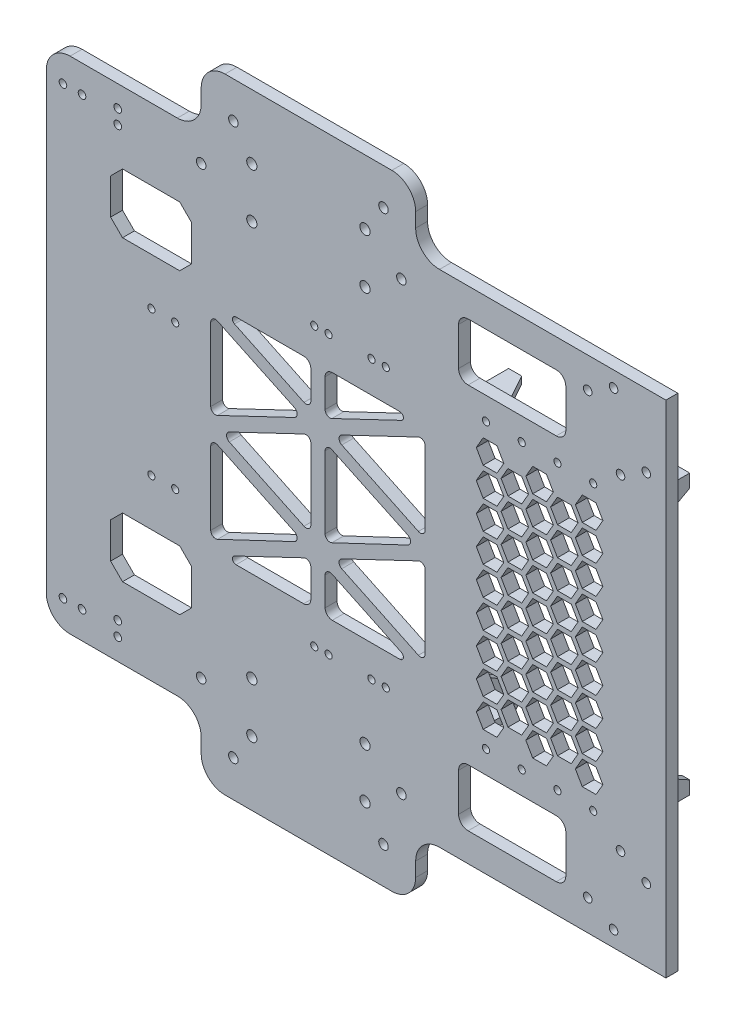
SolidWorks part; units mm, degrees
ref_plane "前视基准面" through (0, 0, 0) normal (0, 0, 1) x (1, 0, 0)
ref_plane "上视基准面" through (0, 0, 0) normal (0, 1, 0) x (1, 0, 0)
ref_plane "右视基准面" through (0, 0, 0) normal (1, 0, 0) x (0, 0, -1)
sketch "草图1" plane through (0, 0, 0) normal (0, 0, 1) x (1, 0, 0)
  line L2 (-130, 95) -> (-130, -95)
  line L3 (-120, -105) -> (-75, -105)
  line L4 (130, 95) -> (130, -95)
  line L5 (126.7518, 102.3765) -> (130, 105) construction
  line L6 (-130, -105) -> (-126.7518, -102.3765) construction
  line L9 (-65, -115) -> (-65, -121)
  line L10 (-55, -131) -> (15, -131)
  line L11 (25, -121) -> (25, -115)
  line L13 (35, -105) -> (120, -105)
  line L14 (126.7518, -102.3765) -> (130, -105) construction
  line L15 (-130, 105) -> (-126.7518, 102.3765) construction
  line L16 (-130, 0) -> (130, 0) construction
  line L17 (35, 105) -> (120, 105)
  line L18 (25, 121) -> (25, 115)
  line L19 (-55, 131) -> (15, 131)
  line L20 (-65, 115) -> (-65, 121)
  line L21 (-120, 105) -> (-75, 105)
  arc A1 (-120, -105) -> (-130, -95) centre (-120, -95) cw
  arc A3 (120, -105) -> (130, -95) centre (120, -95) ccw
  arc A8 (-65, -115) -> (-75, -105) centre (-75, -115) ccw
  arc A9 (25, -115) -> (35, -105) centre (35, -115) cw
  arc A10 (-55, -131) -> (-65, -121) centre (-55, -121) cw
  arc A11 (15, -131) -> (25, -121) centre (15, -121) ccw
  arc A12 (15, 131) -> (25, 121) centre (15, 121) cw
  arc A13 (-55, 131) -> (-65, 121) centre (-55, 121) ccw
  arc A14 (25, 115) -> (35, 105) centre (35, 115) ccw
  arc A15 (-65, 115) -> (-75, 105) centre (-75, 115) cw
  arc A16 (120, 105) -> (130, 95) centre (120, 95) cw
  arc A17 (-120, 105) -> (-130, 95) centre (-120, 95) ccw
  point P0 (0, 0)
  point P40 (25, -105)
  point P45 (25, 105)
  dimension "D2" = 10
  dimension "D3" = 65
  dimension "D4" = 10
  dimension "D5" = 105
  dimension "D7" = 10
  dimension "D8" = 10
  dimension "D10" = 10
  dimension "D12" = 10
  dimension "D13" = 105
  dimension "D18" = 90
  dimension "D19" = 6
extrude "凸台-拉伸1" add sketch "草图1" along normal blind 5
sketch "草图4" plane through (0, 0, 0) normal (0, 0, -1) x (-1, 0, 0)
  line L0 (-39, -47.5) -> (-39, -58.5)
  line L1 (-39, -58.5) -> (-50, -58.5)
  line L2 (-50, -58.5) -> (-50, -55.5)
  line L3 (-50, -55.5) -> (-42, -55.5)
  line L4 (-42, -55.5) -> (-42, -47.5)
  line L5 (-42, -47.5) -> (-39, -47.5)
  line L6 (-130, 0) -> (-25.5592, 0) construction
  line L7 (-130, -95) -> (-130, 95) construction
  line L10 (-130, -95) -> (-130, 95) construction
  dimension "D1" = 11
  dimension "D2" = 11
  dimension "D3" = 3
  dimension "D4" = 3
  dimension "D5" = 80
  dimension "D7" = 55.5
extrude "凸台-拉伸2" add sketch "草图4" along normal blind 20
sketch "草图5" plane through (0, -58.5, 0) normal (0, -1, 0) x (1, 0, 0)
  line L0 (50, -10) -> (44.5, -20)
  line L1 (50, -20) -> (50, 0) construction
  line L2 (50, -20) -> (39, -20) construction
  line L3 (44.5, -20) -> (50, -20)
  line L4 (50, -20) -> (50, -10)
  dimension "D1" = 10
  dimension "D2" = 5.5
extrude "切除-拉伸3" cut sketch "草图5" against normal blind 10
sketch "草图6" plane through (39, 0, 0) normal (-1, 0, 0) x (0, 0, 1)
  line L0 (-20, -53) -> (-10, -47.5)
  line L1 (-20, -58.5) -> (-20, -47.5) construction
  line L2 (-20, -47.5) -> (0, -47.5) construction
  line L3 (-10, -47.5) -> (-20, -47.5)
  line L4 (-20, -47.5) -> (-20, -53)
  dimension "D1" = 10
  dimension "D2" = 5.5
extrude "切除-拉伸4" cut sketch "草图6" against normal blind 10
ref_plane "基准面2" through (77, 0, 0) normal (1, 0, 0) x (0, 0, -1)
mirror "镜向1" about plane through (77, 0, 0) normal (1, 0, 0) of "凸台-拉伸2", "切除-拉伸4", "切除-拉伸3"
mirror "镜向2" about plane through (0, 0, 0) normal (0, 1, 0) of "镜向1"
sketch "草图7" plane through (0, 0, 0) normal (0, 0, -1) x (-1, 0, 0)
  line L4 (-112, -55.5) -> (-104, -55.5) construction
  line L5 (-112, 47.5) -> (-112, 55.5) construction
  line L6 (-112, 55.5) -> (-104, 55.5) construction
  line L7 (-92.013, 36) -> (-94.8997, 41)
  line L8 (-94.8997, 41) -> (-100.6732, 41)
  line L9 (-100.6732, 41) -> (-103.56, 36)
  line L10 (-103.56, 36) -> (-100.6732, 31)
  line L11 (-100.6732, 31) -> (-94.8997, 31)
  line L12 (-94.8997, 31) -> (-92.013, 36)
  line L13 (-77.0019, 36) -> (-97.7865, 36) construction
  line L14 (-74.1151, 31) -> (-71.2284, 36)
  line L15 (-71.2284, 36) -> (-74.1151, 41)
  line L16 (-74.1151, 41) -> (-79.8886, 41)
  line L17 (-79.8886, 41) -> (-82.7754, 36)
  line L18 (-82.7754, 36) -> (-79.8886, 31)
  line L19 (-79.8886, 31) -> (-74.1151, 31)
  line L20 (-92.013, 24) -> (-94.8997, 29)
  line L21 (-93.1677, 30) -> (-90.2809, 25)
  line L22 (-90.2809, 25) -> (-84.5074, 25)
  line L23 (-84.5074, 25) -> (-81.6207, 30)
  line L24 (-81.6207, 30) -> (-84.5074, 35)
  line L25 (-84.5074, 35) -> (-90.2809, 35)
  line L26 (-90.2809, 35) -> (-93.1677, 30)
  line L27 (-84.5074, 37) -> (-81.6207, 42)
  line L28 (-81.6207, 42) -> (-84.5074, 47)
  line L29 (-84.5074, 47) -> (-90.2809, 47)
  line L30 (-90.2809, 47) -> (-93.1677, 42)
  line L31 (-93.1677, 42) -> (-90.2809, 37)
  line L32 (-90.2809, 37) -> (-84.5074, 37)
  line L33 (-79.8886, 43) -> (-74.1151, 43)
  line L34 (-74.1151, 43) -> (-71.2284, 48)
  line L35 (-71.2284, 48) -> (-74.1151, 53)
  line L36 (-74.1151, 53) -> (-79.8886, 53)
  line L37 (-79.8886, 53) -> (-82.7754, 48)
  line L38 (-82.7754, 48) -> (-79.8886, 43)
  line L39 (-94.8997, 43) -> (-92.013, 48)
  line L40 (-92.013, 48) -> (-94.8997, 53)
  line L41 (-94.8997, 53) -> (-100.6732, 53)
  line L42 (-100.6732, 53) -> (-103.56, 48)
  line L43 (-103.56, 48) -> (-100.6732, 43)
  line L44 (-100.6732, 43) -> (-94.8997, 43)
  line L45 (-72.3831, 42) -> (-69.4963, 37)
  line L46 (-69.4963, 37) -> (-63.7228, 37)
  line L47 (-63.7228, 37) -> (-60.8361, 42)
  line L48 (-60.8361, 42) -> (-63.7228, 47)
  line L49 (-63.7228, 47) -> (-69.4963, 47)
  line L50 (-69.4963, 47) -> (-72.3831, 42)
  line L51 (-94.8997, 29) -> (-100.6732, 29)
  line L52 (-100.6732, 29) -> (-103.56, 24)
  line L53 (-103.56, 24) -> (-100.6732, 19)
  line L54 (-100.6732, 19) -> (-94.8997, 19)
  line L55 (-94.8997, 19) -> (-92.013, 24)
  line L56 (-93.1677, 18) -> (-90.2809, 13)
  line L57 (-90.2809, 13) -> (-84.5074, 13)
  line L58 (-84.5074, 13) -> (-81.6207, 18)
  line L59 (-81.6207, 18) -> (-84.5074, 23)
  line L60 (-84.5074, 23) -> (-90.2809, 23)
  line L61 (-90.2809, 23) -> (-93.1677, 18)
  line L62 (-74.1151, 19) -> (-71.2284, 24)
  line L63 (-71.2284, 24) -> (-74.1151, 29)
  line L64 (-74.1151, 29) -> (-79.8886, 29)
  line L65 (-79.8886, 29) -> (-82.7754, 24)
  line L66 (-82.7754, 24) -> (-79.8886, 19)
  line L67 (-79.8886, 19) -> (-74.1151, 19)
  line L68 (-72.3831, 30) -> (-69.4963, 25)
  line L69 (-69.4963, 25) -> (-63.7228, 25)
  line L70 (-63.7228, 25) -> (-60.8361, 30)
  line L71 (-60.8361, 30) -> (-63.7228, 35)
  line L72 (-63.7228, 35) -> (-69.4963, 35)
  line L73 (-69.4963, 35) -> (-72.3831, 30)
  line L74 (-92.013, 12) -> (-94.8997, 17)
  line L75 (-94.8997, 17) -> (-100.6732, 17)
  line L76 (-100.6732, 17) -> (-103.56, 12)
  line L77 (-103.56, 12) -> (-100.6732, 7)
  line L78 (-100.6732, 7) -> (-94.8997, 7)
  line L79 (-94.8997, 7) -> (-92.013, 12)
  line L80 (-93.1677, 6) -> (-90.2809, 1)
  line L81 (-90.2809, 1) -> (-84.5074, 1)
  line L82 (-84.5074, 1) -> (-81.6207, 6)
  line L83 (-81.6207, 6) -> (-84.5074, 11)
  line L84 (-84.5074, 11) -> (-90.2809, 11)
  line L85 (-90.2809, 11) -> (-93.1677, 6)
  line L86 (-74.1151, 7) -> (-71.2284, 12)
  line L87 (-71.2284, 12) -> (-74.1151, 17)
  line L88 (-74.1151, 17) -> (-79.8886, 17)
  line L89 (-79.8886, 17) -> (-82.7754, 12)
  line L90 (-82.7754, 12) -> (-79.8886, 7)
  line L91 (-79.8886, 7) -> (-74.1151, 7)
  line L92 (-72.3831, 18) -> (-69.4963, 13)
  line L93 (-69.4963, 13) -> (-63.7228, 13)
  line L94 (-63.7228, 13) -> (-60.8361, 18)
  line L95 (-60.8361, 18) -> (-63.7228, 23)
  line L96 (-63.7228, 23) -> (-69.4963, 23)
  line L97 (-69.4963, 23) -> (-72.3831, 18)
  line L98 (-92.013, 0) -> (-94.8997, 5)
  line L99 (-94.8997, 5) -> (-100.6732, 5)
  line L100 (-100.6732, 5) -> (-103.56, 0)
  line L101 (-103.56, 0) -> (-100.6732, -5)
  line L102 (-100.6732, -5) -> (-94.8997, -5)
  line L103 (-94.8997, -5) -> (-92.013, 0)
  line L104 (-93.1677, -6) -> (-90.2809, -11)
  line L105 (-90.2809, -11) -> (-84.5074, -11)
  line L106 (-84.5074, -11) -> (-81.6207, -6)
  line L107 (-81.6207, -6) -> (-84.5074, -1)
  line L108 (-84.5074, -1) -> (-90.2809, -1)
  line L109 (-90.2809, -1) -> (-93.1677, -6)
  line L110 (-74.1151, -5) -> (-71.2284, 0)
  line L111 (-71.2284, 0) -> (-74.1151, 5)
  line L112 (-74.1151, 5) -> (-79.8886, 5)
  line L113 (-79.8886, 5) -> (-82.7754, 0)
  line L114 (-82.7754, 0) -> (-79.8886, -5)
  line L115 (-79.8886, -5) -> (-74.1151, -5)
  line L116 (-72.3831, 6) -> (-69.4963, 1)
  line L117 (-69.4963, 1) -> (-63.7228, 1)
  line L118 (-63.7228, 1) -> (-60.8361, 6)
  line L119 (-60.8361, 6) -> (-63.7228, 11)
  line L120 (-63.7228, 11) -> (-69.4963, 11)
  line L121 (-69.4963, 11) -> (-72.3831, 6)
  line L122 (-92.013, -12) -> (-94.8997, -7)
  line L123 (-94.8997, -7) -> (-100.6732, -7)
  line L124 (-100.6732, -7) -> (-103.56, -12)
  line L125 (-103.56, -12) -> (-100.6732, -17)
  line L126 (-100.6732, -17) -> (-94.8997, -17)
  line L127 (-94.8997, -17) -> (-92.013, -12)
  line L128 (-93.1677, -18) -> (-90.2809, -23)
  line L129 (-90.2809, -23) -> (-84.5074, -23)
  line L130 (-84.5074, -23) -> (-81.6207, -18)
  line L131 (-81.6207, -18) -> (-84.5074, -13)
  line L132 (-84.5074, -13) -> (-90.2809, -13)
  line L133 (-90.2809, -13) -> (-93.1677, -18)
  line L134 (-74.1151, -17) -> (-71.2284, -12)
  line L135 (-71.2284, -12) -> (-74.1151, -7)
  line L136 (-74.1151, -7) -> (-79.8886, -7)
  line L137 (-79.8886, -7) -> (-82.7754, -12)
  line L138 (-82.7754, -12) -> (-79.8886, -17)
  line L139 (-79.8886, -17) -> (-74.1151, -17)
  line L140 (-72.3831, -6) -> (-69.4963, -11)
  line L141 (-69.4963, -11) -> (-63.7228, -11)
  line L142 (-63.7228, -11) -> (-60.8361, -6)
  line L143 (-60.8361, -6) -> (-63.7228, -1)
  line L144 (-63.7228, -1) -> (-69.4963, -1)
  line L145 (-69.4963, -1) -> (-72.3831, -6)
  line L146 (-92.013, -24) -> (-94.8997, -19)
  line L147 (-94.8997, -19) -> (-100.6732, -19)
  line L148 (-100.6732, -19) -> (-103.56, -24)
  line L149 (-103.56, -24) -> (-100.6732, -29)
  line L150 (-100.6732, -29) -> (-94.8997, -29)
  line L151 (-94.8997, -29) -> (-92.013, -24)
  line L152 (-93.1677, -30) -> (-90.2809, -35)
  line L153 (-90.2809, -35) -> (-84.5074, -35)
  line L154 (-84.5074, -35) -> (-81.6207, -30)
  line L155 (-81.6207, -30) -> (-84.5074, -25)
  line L156 (-84.5074, -25) -> (-90.2809, -25)
  line L157 (-90.2809, -25) -> (-93.1677, -30)
  line L158 (-74.1151, -29) -> (-71.2284, -24)
  line L159 (-71.2284, -24) -> (-74.1151, -19)
  line L160 (-74.1151, -19) -> (-79.8886, -19)
  line L161 (-79.8886, -19) -> (-82.7754, -24)
  line L162 (-82.7754, -24) -> (-79.8886, -29)
  line L163 (-79.8886, -29) -> (-74.1151, -29)
  line L164 (-72.3831, -18) -> (-69.4963, -23)
  line L165 (-69.4963, -23) -> (-63.7228, -23)
  line L166 (-63.7228, -23) -> (-60.8361, -18)
  line L167 (-60.8361, -18) -> (-63.7228, -13)
  line L168 (-63.7228, -13) -> (-69.4963, -13)
  line L169 (-69.4963, -13) -> (-72.3831, -18)
  line L170 (-92.013, -36) -> (-94.8997, -31)
  line L171 (-94.8997, -31) -> (-100.6732, -31)
  line L172 (-100.6732, -31) -> (-103.56, -36)
  line L173 (-103.56, -36) -> (-100.6732, -41)
  line L174 (-100.6732, -41) -> (-94.8997, -41)
  line L175 (-94.8997, -41) -> (-92.013, -36)
  line L176 (-93.1677, -42) -> (-90.2809, -47)
  line L177 (-90.2809, -47) -> (-84.5074, -47)
  line L178 (-84.5074, -47) -> (-81.6207, -42)
  line L179 (-81.6207, -42) -> (-84.5074, -37)
  line L180 (-84.5074, -37) -> (-90.2809, -37)
  line L181 (-90.2809, -37) -> (-93.1677, -42)
  line L182 (-74.1151, -41) -> (-71.2284, -36)
  line L183 (-71.2284, -36) -> (-74.1151, -31)
  line L184 (-74.1151, -31) -> (-79.8886, -31)
  line L185 (-79.8886, -31) -> (-82.7754, -36)
  line L186 (-82.7754, -36) -> (-79.8886, -41)
  line L187 (-79.8886, -41) -> (-74.1151, -41)
  line L188 (-72.3831, -30) -> (-69.4963, -35)
  line L189 (-69.4963, -35) -> (-63.7228, -35)
  line L190 (-63.7228, -35) -> (-60.8361, -30)
  line L191 (-60.8361, -30) -> (-63.7228, -25)
  line L192 (-63.7228, -25) -> (-69.4963, -25)
  line L193 (-69.4963, -25) -> (-72.3831, -30)
  line L194 (-92.013, -48) -> (-94.8997, -43)
  line L195 (-94.8997, -43) -> (-100.6732, -43)
  line L196 (-100.6732, -43) -> (-103.56, -48)
  line L197 (-103.56, -48) -> (-100.6732, -53)
  line L198 (-100.6732, -53) -> (-94.8997, -53)
  line L199 (-94.8997, -53) -> (-92.013, -48)
  line L206 (-74.1151, -53) -> (-71.2284, -48)
  line L207 (-71.2284, -48) -> (-74.1151, -43)
  line L208 (-74.1151, -43) -> (-79.8886, -43)
  line L209 (-79.8886, -43) -> (-82.7754, -48)
  line L210 (-82.7754, -48) -> (-79.8886, -53)
  line L211 (-79.8886, -53) -> (-74.1151, -53)
  line L212 (-72.3831, -42) -> (-69.4963, -47)
  line L213 (-69.4963, -47) -> (-63.7228, -47)
  line L214 (-63.7228, -47) -> (-60.8361, -42)
  line L215 (-60.8361, -42) -> (-63.7228, -37)
  line L216 (-63.7228, -37) -> (-69.4963, -37)
  line L217 (-69.4963, -37) -> (-72.3831, -42)
  line L218 (-61.9908, 36) -> (-59.104, 31)
  line L219 (-61.9908, 48) -> (-59.104, 43)
  line L220 (-59.104, 43) -> (-53.3305, 43)
  line L221 (-53.3305, 43) -> (-50.4438, 48)
  line L222 (-50.4438, 48) -> (-53.3305, 53)
  line L223 (-53.3305, 53) -> (-59.104, 53)
  line L224 (-59.104, 53) -> (-61.9908, 48)
  line L225 (-59.104, 31) -> (-53.3305, 31)
  line L226 (-53.3305, 31) -> (-50.4438, 36)
  line L227 (-50.4438, 36) -> (-53.3305, 41)
  line L228 (-53.3305, 41) -> (-59.104, 41)
  line L229 (-59.104, 41) -> (-61.9908, 36)
  line L230 (-61.9908, 24) -> (-59.104, 19)
  line L231 (-59.104, 19) -> (-53.3305, 19)
  line L232 (-53.3305, 19) -> (-50.4438, 24)
  line L233 (-50.4438, 24) -> (-53.3305, 29)
  line L234 (-53.3305, 29) -> (-59.104, 29)
  line L235 (-59.104, 29) -> (-61.9908, 24)
  line L236 (-61.9908, 12) -> (-59.104, 7)
  line L237 (-59.104, 7) -> (-53.3305, 7)
  line L238 (-53.3305, 7) -> (-50.4438, 12)
  line L239 (-50.4438, 12) -> (-53.3305, 17)
  line L240 (-53.3305, 17) -> (-59.104, 17)
  line L241 (-59.104, 17) -> (-61.9908, 12)
  line L242 (-61.9908, 0) -> (-59.104, -5)
  line L243 (-59.104, -5) -> (-53.3305, -5)
  line L244 (-53.3305, -5) -> (-50.4438, 0)
  line L245 (-50.4438, 0) -> (-53.3305, 5)
  line L246 (-53.3305, 5) -> (-59.104, 5)
  line L247 (-59.104, 5) -> (-61.9908, 0)
  line L248 (-61.9908, -12) -> (-59.104, -17)
  line L249 (-59.104, -17) -> (-53.3305, -17)
  line L250 (-53.3305, -17) -> (-50.4438, -12)
  line L251 (-50.4438, -12) -> (-53.3305, -7)
  line L252 (-53.3305, -7) -> (-59.104, -7)
  line L253 (-59.104, -7) -> (-61.9908, -12)
  line L254 (-61.9908, -24) -> (-59.104, -29)
  line L255 (-59.104, -29) -> (-53.3305, -29)
  line L256 (-53.3305, -29) -> (-50.4438, -24)
  line L257 (-50.4438, -24) -> (-53.3305, -19)
  line L258 (-53.3305, -19) -> (-59.104, -19)
  line L259 (-59.104, -19) -> (-61.9908, -24)
  line L260 (-61.9908, -36) -> (-59.104, -41)
  line L261 (-59.104, -41) -> (-53.3305, -41)
  line L262 (-53.3305, -41) -> (-50.4438, -36)
  line L263 (-50.4438, -36) -> (-53.3305, -31)
  line L264 (-53.3305, -31) -> (-59.104, -31)
  line L265 (-59.104, -31) -> (-61.9908, -36)
  line L266 (-61.9908, -48) -> (-59.104, -53)
  line L267 (-59.104, -53) -> (-53.3305, -53)
  line L268 (-53.3305, -53) -> (-50.4438, -48)
  line L269 (-50.4438, -48) -> (-53.3305, -43)
  line L270 (-53.3305, -43) -> (-59.104, -43)
  line L271 (-59.104, -43) -> (-61.9908, -48)
  line L272 (-93.1677, -54) -> (-90.2809, -59) [skipped]
  line L273 (-90.2809, -59) -> (-84.5074, -59) [skipped]
  line L274 (-84.5074, -59) -> (-81.6207, -54) [skipped]
  line L275 (-81.6207, -54) -> (-84.5074, -49) [skipped]
  line L276 (-84.5074, -49) -> (-90.2809, -49) [skipped]
  line L277 (-90.2809, -49) -> (-93.1677, -54) [skipped]
  circle A0 centre (-97.7865, 36) radius 5 construction
  circle A1 centre (-77.0019, 36) radius 5 construction
  circle A2 centre (-87.3942, 30) radius 5 construction
  circle A3 centre (-87.3942, 42) radius 5 construction
  circle A4 centre (-77.0019, 48) radius 5 construction
  circle A5 centre (-97.7865, 48) radius 5 construction
  circle A6 centre (-66.6096, 42) radius 5 construction
  circle A7 centre (-56.2173, 48) radius 5 construction
  point P4 (-87.3942, 37)
  dimension "D1" = 2
  dimension "D3" = 10
  dimension "D4" = 10
  dimension "D5" = 2
  dimension "D7" = 10
  dimension "D11" = 10
  dimension "D14" = 10
  dimension "D15" = 10
  dimension "D20" = 10
  dimension "D2" = 2
  dimension "D6" = 2
  dimension "D8" = 2
  dimension "D9" = 2
  dimension "D10" = 2
  dimension "D12" = 2
  dimension "D13" = 2
  dimension "D16" = 2
  dimension "D17" = 2
  dimension "D19" = 2
  dimension "D21" = 9
  dimension "D22" = 2.5
  dimension "D23" = 2.5
  dimension "D24" = 8.44
  dimension "D18" = 8
extrude "切除-拉伸5" cut sketch "草图7" against normal blind 5
sketch "草图8" plane through (0, 0, 0) normal (0, 0, -1) x (-1, 0, 0)
  line L0 (-75.3677, 120) -> (-75.3677, -120)
  line L1 (-100.0285, 77.2863) -> (-100.0285, -77.2863)
  line L2 (-100.0285, 77.2863) -> (-75.3677, 120)
  line L3 (-100.0285, -77.2863) -> (-75.3677, -120)
  line L4 (-37.1297, 0) -> (-146.8562, 0) construction
  dimension "D1" = 30
  dimension "D2" = 30
  dimension "D3" = 120
  dimension "D4" = 120
sketch "草图9" plane through (0, 0, 0) normal (0, 0, -1) x (-1, 0, 0)
  line L0 (148.8518, 0) -> (-37.1297, 0) construction
  line L1 (-29, 41) -> (-29, 4)
  line L2 (-25, -45) -> (13, -45)
  line L3 (61, -41) -> (61, -4)
  line L4 (57, 45) -> (19, 45)
  line L14 (-29, 41) -> (9.8049, 22.5)
  line L15 (57, 0) -> (19, -18.1163)
  line L16 (130, 95) -> (130, -95) construction
  line L17 (63, 93) -> (118, 93)
  line L18 (63, 93) -> (63, 66)
  line L19 (63, 66) -> (118, 66)
  line L20 (118, 93) -> (118, 66)
  line L21 (75, 105) -> (120, 105) construction
  line L22 (63, -66) -> (118, -66)
  line L23 (118, -93) -> (118, -66)
  line L24 (63, -93) -> (118, -93)
  line L25 (63, -93) -> (63, -66)
  line L26 (-120, 105) -> (-35, 105) construction
  line L27 (-43, 93) -> (-88, 93)
  line L28 (-43, 93) -> (-43, 69)
  line L29 (-43, 69) -> (-88, 69)
  line L30 (-88, 93) -> (-88, 69)
  line L31 (-130, -95) -> (-130, 95) construction
  line L32 (-43, -69) -> (-88, -69)
  line L33 (-88, -93) -> (-88, -69)
  line L34 (-43, -93) -> (-88, -93)
  line L35 (-43, -93) -> (-43, -69)
  line L36 (-25, 45) -> (13, 26.8837)
  line L37 (-25, -45) -> (13, -26.8837)
  line L38 (61, 41) -> (22.0746, 22.5575)
  line L39 (-25.5359, 0) -> (13, -18.258)
  line L40 (57, 45) -> (19, 26.8837)
  line L41 (57, -45) -> (19, -26.8837)
  line L42 (16, 61.4977) -> (16, -60.5731) construction
  line L43 (13, 45) -> (13, 26.8837)
  line L44 (19, 45) -> (19, 26.8837)
  line L45 (13, 18.258) -> (13, -18.258)
  line L46 (9.8049, 22.5) -> (-29, 4)
  line L47 (19, 18.1163) -> (57, 0)
  line L48 (22.0746, 22.5575) -> (61, 4)
  line L49 (13, 18.258) -> (-25.5359, 0)
  line L50 (19, 18.1163) -> (19, -18.1163)
  line L51 (22.0746, -22.5575) -> (61, -41)
  line L52 (9.8049, -22.5) -> (-29, -41)
  line L53 (9.8049, -22.5) -> (-29, -4)
  line L54 (22.0746, -22.5575) -> (61, -4)
  line L55 (13, -26.8837) -> (13, -45)
  line L56 (19, -26.8837) -> (19, -45)
  line L57 (13, 45) -> (-25, 45)
  line L58 (-29, -4) -> (-29, -41)
  line L59 (19, -45) -> (57, -45)
  line L60 (61, 4) -> (61, 41)
  line L61 (-44, 41) -> (-44, -37.8122) construction
  dimension "D1" = 45
  dimension "D2" = 45
  dimension "D3" = 15
  dimension "D4" = 90
  dimension "D5" = 1
  dimension "D7" = 12
  dimension "D8" = 12
  dimension "D9" = 27
  dimension "D10" = 55
  dimension "D11" = 12
  dimension "D12" = 45
  dimension "D13" = 42
  dimension "D14" = 24
  dimension "D21" = 4
  dimension "D22" = 4
  dimension "D23" = 4
  dimension "D24" = 4
  dimension "D26" = 4
  dimension "D27" = 3
  dimension "D28" = 45
extrude "切除-拉伸6" cut sketch "草图9" against normal blind 5 contours L27 L30 L29 L28 | L34 L35 L32 L33 | L4 L44 L40 | L48 L60 L38 | L47 L50 L15 | L54 L51 L3 | L56 L59 L41 | L55 L37 L2 | L53 L58 L52 | L45 L49 L39 | L46 L14 L1 | L43 L57 L36 | L57 L36 L43 region at (16.065, 22.5, 0) region at (-0.3333, -38.9612, 0) region at (-48.0249, -22.5192, 0) region at (-31.6667, 38.9612, 0) region at (-31.6667, 0, 0) region at (65.5, 81, 0) region at (65.5, -81, 0) region at (-0.3333, 38.9612, 0) region at (-48.0249, 22.5192, 0) region at (-0.1547, 0, 0) region at (-31.6667, -38.9612, 0) region at (16.065, -22.5, 0)
fillet "圆角1" radius 4 8 edges at (43, -93, 2.5) (88, -69, 2.5) (43, -69, 2.5) (88, -93, 2.5) (88, 69, 2.5) (43, 69, 2.5) (43, 93, 2.5) (88, 93, 2.5)
fillet "圆角2" radius 1.5 4 edges at (25, -45, 2.5) (-57, -45, 2.5) (25, 45, 2.5) (-57, 45, 2.5)
fillet "圆角3" radius 2 22 edges at (29, -4, 2.5) (29, 4, 2.5) (-13, -18.258, 2.5) (-61, -41, 2.5) (-61, 4, 2.5) (-13, -26.8837, 2.5) (-13, 18.258, 2.5) (-61, -4, 2.5) (-22.0746, -22.5575, 2.5) (25.5359, 0, 2.5) (-22.0746, 22.5575, 2.5) (-61, 41, 2.5) (-19, 26.8837, 2.5) (-19, -26.8837, 2.5) (-19, -18.1163, 2.5) (29, -41, 2.5) (29, 41, 2.5) (-57, 0, 2.5) (-9.8049, -22.5, 2.5) (-13, 26.8837, 2.5) (-9.8049, 22.5, 2.5) (-19, 18.1163, 2.5)
fillet "圆角4" radius 3 4 edges at (-13, -45, 2.5) (-13, 45, 2.5) (-19, -45, 2.5) (-19, 45, 2.5)
sketch "草图12" plane through (0, 0, 0) normal (0, 0, -1) x (-1, 0, 0)
  line L1 (-120, 105) -> (-130, 105)
  line L2 (-120, 105) -> (-120, -105)
  line L3 (-120, -105) -> (-130, -105)
  line L4 (-130, 105) -> (-130, -105)
extrude "凸台-拉伸3" add sketch "草图12" against normal up to surface (5 mm away) up to face at (65.5, 81, 5)
hole_wizard "M3 六角头螺栓的柱形沉头孔1" positions "草图16" profile "草图17" counterbore size "M3" standard "GB" end condition through all
sketch "草图16" plane through (-124.3639, -131.0101, -4.2) normal (0, 0, -1) x (0, 1, 0)
  point P0 (221.0101, 24.3639)
  point P3 (227.0101, 24.3639)
sketch "草图17" plane through (-100, 90, -4.2) normal (1, 0, 0) x (0, 1, 0)
  line L0 (0, 0) -> (0, 9.2)
  line L1 (0, 9.2) -> (1.6, 9.2)
  line L2 (1.6, 9.2) -> (1.6, 1.6)
  line L3 (1.6, 1.6) -> (2.95, 1.6)
  line L4 (2.95, 1.6) -> (2.95, 0)
  line L5 (2.95, 0) -> (0, 0)
  line L6 (0, -6.35) -> (0, 107.95) construction
  dimension "通孔孔直径" = 3.2
  dimension "通孔孔深度" = 9.2
  dimension "柱形沉头孔直径" = 5.9
  dimension "柱形沉头孔深度" = 1.6
sketch "草图10" plane through (0, 0, 0) normal (0, 0, -1) x (-1, 0, 0)
  line L0 (-37.1297, 0) -> (-146.8562, 0) construction
  line L1 (-37.1297, 0) -> (-146.8562, 0) construction
  circle A0 centre (-121.782, 74.6081) radius 1.8 construction
  circle A1 centre (-110.9567, 68.3581) radius 1.8 construction
  circle A2 centre (-108.032, 98.4238) radius 1.8 construction
  circle A3 centre (-97.2067, 92.1738) radius 1.8 construction
  circle A4 centre (-3.75, 104) radius 2.15 construction
  circle A5 centre (-3.75, 104) radius 2.15
  circle A6 centre (-3.75, -104) radius 2.15
  circle A7 centre (115, 93.5) radius 1.6 construction
  circle A8 centre (123, 93.5) radius 1.6 construction
  circle A9 centre (115, 93.5) radius 1.6
  circle A10 centre (123, 93.5) radius 1.6
  circle A11 centre (123, -93.5) radius 1.6
  circle A12 centre (115, -93.5) radius 1.6
  circle A13 centre (100, 96) radius 1.6 construction
  circle A14 centre (100, 90) radius 1.6 construction
  circle A15 centre (-121.782, 74.6081) radius 1.8
  circle A16 centre (-110.9567, 68.3581) radius 1.8
  circle A17 centre (-108.032, 98.4238) radius 1.8
  circle A18 centre (-97.2067, 92.1738) radius 1.8
  circle A41 centre (-97.2067, -92.1738) radius 1.8
  circle A42 centre (-108.032, -98.4238) radius 1.8
  circle A43 centre (-110.9567, -68.3581) radius 1.8
  circle A44 centre (-121.782, -74.6081) radius 1.8
  circle A45 centre (-99.5, 59.5) radius 1.5 construction
  circle A46 centre (-84.5, 59.5) radius 1.5 construction
  circle A47 centre (-69.5, 59.5) radius 1.5 construction
  circle A48 centre (-54.5, 59.5) radius 1.5 construction
  circle A49 centre (-12.4571, 58.25) radius 1.5 construction
  circle A50 centre (-6.4571, 58.25) radius 1.5 construction
  circle A51 centre (11.5429, 58.25) radius 1.5 construction
  circle A52 centre (17.5429, 58.25) radius 1.5 construction
  circle A53 centre (-99.5, 59.5) radius 1.5
  circle A54 centre (-84.5, 59.5) radius 1.5
  circle A55 centre (-69.5, 59.5) radius 1.5
  circle A56 centre (-54.5, 59.5) radius 1.5
  circle A57 centre (-12.4571, 58.25) radius 1.5
  circle A58 centre (-6.4571, 58.25) radius 1.5
  circle A59 centre (11.5429, 58.25) radius 1.5
  circle A60 centre (17.5429, 58.25) radius 1.5
  circle A61 centre (17.5429, -58.25) radius 1.5
  circle A62 centre (11.5429, -58.25) radius 1.5
  circle A63 centre (-6.4571, -58.25) radius 1.5
  circle A64 centre (-12.4571, -58.25) radius 1.5
  circle A65 centre (-54.5, -59.5) radius 1.5
  circle A66 centre (-69.5, -59.5) radius 1.5
  circle A67 centre (-84.5, -59.5) radius 1.5
  circle A68 centre (-99.5, -59.5) radius 1.5
  circle A69 centre (100, 96) radius 1.6
  circle A70 centre (100, 90) radius 1.6
  circle A71 centre (100, -90) radius 1.6
  circle A72 centre (100, -96) radius 1.6
  circle A89 centre (75.897, 30.3) radius 1.5 construction
  circle A90 centre (85.897, 30.3) radius 1.5 construction
  circle A91 centre (75.897, 30.3) radius 1.5
  circle A92 centre (85.897, 30.3) radius 1.5
  circle A93 centre (85.897, -30.3) radius 1.5
  circle A94 centre (75.897, -30.3) radius 1.5
  circle A95 centre (43.75, 83) radius 2.15 construction
  circle A96 centre (43.75, 104) radius 2.15 construction
  circle A97 centre (-3.75, 83) radius 2.15 construction
  circle A99 centre (43.75, 83) radius 2.15
  circle A100 centre (43.75, 104) radius 2.15
  circle A101 centre (-3.75, 83) radius 2.15
  circle A104 centre (-3.75, -83) radius 2.15
  circle A105 centre (43.75, -104) radius 2.15
  circle A106 centre (43.75, -83) radius 2.15
extrude "切除-拉伸7" cut sketch "草图10" against normal through all
sketch "草图11" plane through (0, 0, 0) normal (0, 0, -1) x (-1, 0, 0)
  line L0 (130, 95) -> (130, -95) construction
  line L1 (74, -75) -> (98, -75)
  line L2 (69, -70) -> (69, -55)
  line L3 (74, -50) -> (98, -50)
  line L4 (103, -70) -> (103, -55)
  line L5 (130, 0) -> (108.529, 0) construction
  line L10 (69, -70) -> (74, -75)
  line L11 (69, -55) -> (74, -50)
  line L12 (98, -50) -> (103, -55)
  line L13 (98, -75) -> (103, -70)
  line L14 (98, 75) -> (103, 70)
  line L15 (98, 50) -> (103, 55)
  line L16 (69, 55) -> (74, 50)
  line L17 (69, 70) -> (74, 75)
  line L18 (103, 70) -> (103, 55)
  line L19 (74, 50) -> (98, 50)
  line L20 (69, 70) -> (69, 55)
  line L21 (74, 75) -> (98, 75)
  point P0 (69, -75)
  point P1 (103, -50)
  point P2 (69, -50)
  point P3 (103, -75)
  point P8 (103, 75)
  point P9 (69, 50)
  point P10 (103, 50)
  point P11 (69, 75)
  dimension "D1" = 34
  dimension "D2" = 25
  dimension "D3" = 27
  dimension "D4" = 50
extrude "切除-拉伸8" cut sketch "草图11" against normal through all
sketch "草图14" plane through (0, 0, 5) normal (0, 0, 1) x (1, 0, 0)
  line L0 (25, -121) -> (25, -115) construction
  line L1 (-55, -131) -> (15, -131) construction
  line L2 (-20, -131) -> (-20, 131) construction
  line L3 (15, 131) -> (-55, 131) construction
  line L4 (-20, 0) -> (-130, 0) construction
  line L5 (-130, 95) -> (-130, -95) construction
  circle A0 centre (11.5, -115.68) radius 2
  circle A1 centre (-51.5, -115.68) radius 2
  circle A2 centre (-51.5, 115.68) radius 2
  circle A3 centre (11.5, 115.68) radius 2
  dimension "D1" = 4
  dimension "D2" = 13.5
  dimension "D3" = 15.32
extrude "切除-拉伸9" cut sketch "草图14" against normal blind 10
sketch "草图15" plane through (0, 0, 0) normal (0, 0, -1) x (-1, 0, 0)
  line L0 (65, -93.5) -> (-19, -93.5) construction
  line L1 (130, 0) -> (-85.2757, 0) construction
  line L2 (130, 95) -> (130, -95) construction
  line L3 (-25, -121) -> (-25, -115) construction
  circle A0 centre (65, -93.5) radius 2
  circle A1 centre (-19, -93.5) radius 2
  circle A2 centre (65, 93.5) radius 2
  circle A3 centre (-19, 93.5) radius 2
  dimension "D1" = 4
  dimension "D3" = 6
  dimension "D2" = 84
extrude "切除-拉伸10" cut sketch "草图15" against normal through all
equation "\"45、\"=43.7672"
